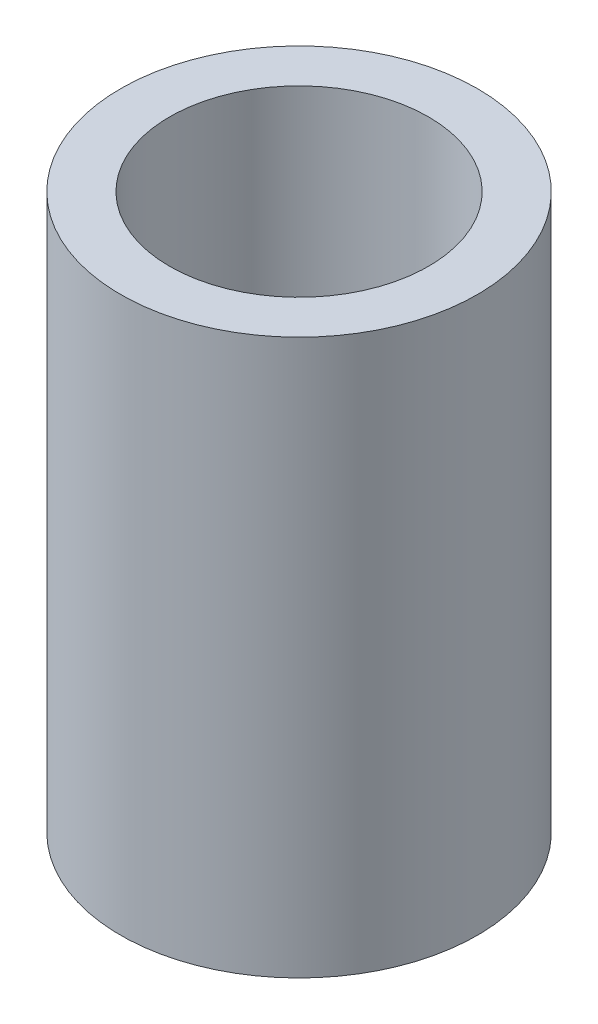
SolidWorks part; units mm, degrees
ref_plane "Front Plane" through (0, 0, 0) normal (0, 0, 1) x (1, 0, 0)
ref_plane "Top Plane" through (0, 0, 0) normal (0, 1, 0) x (1, 0, 0)
ref_plane "Right Plane" through (0, 0, 0) normal (1, 0, 0) x (0, 0, -1)
sketch "Sketch1" plane through (0, 0, 0) normal (0, 1, 0) x (1, 0, 0)
  circle A0 centre (0, 0) radius 6.75
extrude "Boss-Extrude1" add sketch "Sketch1" along normal blind 21
sketch "Sketch2" plane through (0, 21, 0) normal (0, 1, 0) x (1, 0, 0)
  circle A0 centre (0, 0) radius 4.9
extrude "Cut-Extrude1" cut sketch "Sketch2" against normal blind 10
sketch "Sketch3" plane through (0, 0, 0) normal (0, -1, 0) x (1, 0, 0)
  line L1 (-0.882, -1.2133) -> (1.358, -0.6371)
  arc A0 (1.358, -0.6371) -> (-0.882, -1.2133) centre (0, 0) ccw
  dimension "D1" = 2.24
extrude "Cut-Extrude2" cut sketch "Sketch3" against normal blind 8
